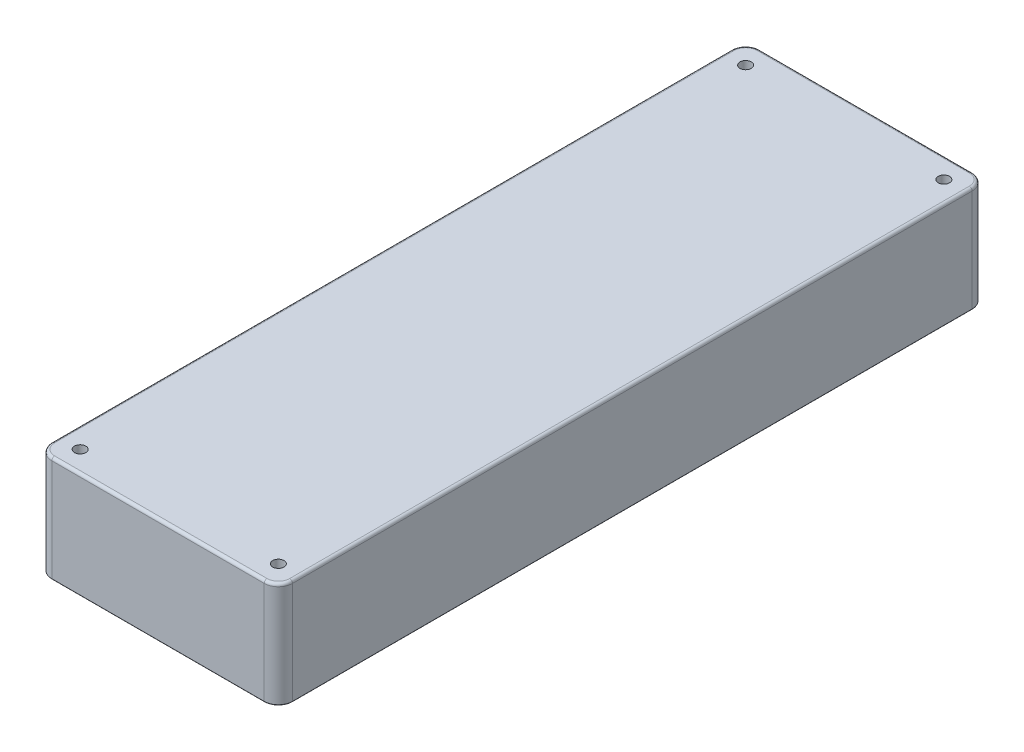
SolidWorks part; units mm, degrees
ref_plane "Front Plane" through (0, 0, 0) normal (0, 0, 1) x (1, 0, 0)
ref_plane "Top Plane" through (0, 0, 0) normal (0, 1, 0) x (1, 0, 0)
ref_plane "Right Plane" through (0, 0, 0) normal (1, 0, 0) x (0, 0, -1)
sketch "Sketch2" plane through (0, 0, 0) normal (0, 1, 0) x (1, 0, 0)
  line L1 (-42.5, 125) -> (42.5, 125)
  line L2 (-42.5, 125) -> (-42.5, -125)
  line L3 (-42.5, -125) -> (42.5, -125)
  line L4 (42.5, 125) -> (42.5, -125)
  line L5 (-42.5, 125) -> (42.5, -125) construction
  line L6 (-42.5, -125) -> (42.5, 125) construction
  point P0 (0, 0)
  dimension "D1" = 250
  dimension "D2" = 85
extrude "Boss-Extrude1" add sketch "Sketch2" along normal blind 2.25
sketch "Sketch3" plane through (0, 2.25, 0) normal (0, 1, 0) x (1, 0, 0)
  line L0 (0, 0) -> (0, 46.4308) construction
  line L1 (42.5, 125) -> (-42.5, 125) construction
  line L2 (0, 0) -> (-50.5006, 0) construction
  circle A0 centre (-35, 117.5) radius 2
  circle A1 centre (35, 117.5) radius 2
  circle A2 centre (35, -117.5) radius 2
  circle A3 centre (-35, -117.5) radius 2
  dimension "D1" = 4
  dimension "D2" = 70
  dimension "D3" = 7.5
extrude "Cut-Extrude1" cut sketch "Sketch3" against normal up to surface (2.25 mm away) up to face at (0, 0, 0)
fillet "Fillet1" radius 5 4 edges at (42.5, 1.125, 125) (-42.5, 1.125, -125) (42.5, 1.125, -125) (-42.5, 1.125, 125)
sketch "Sketch4" plane through (0, 0, 0) normal (0, -1, 0) x (1, 0, 0)
  line L0 (40.25, -120) -> (40.25, 120)
  line L1 (37.5, 122.75) -> (-37.5, 122.75)
  line L2 (-40.25, 120) -> (-40.25, -120)
  line L3 (-37.5, -122.75) -> (37.5, -122.75)
  line L4 (42.5, -120) -> (42.5, 120)
  line L5 (37.5, 125) -> (-37.5, 125)
  line L6 (-42.5, 120) -> (-42.5, -120)
  line L7 (-37.5, -125) -> (37.5, -125)
  line L8 (42.5, -120) -> (42.5, 120)
  line L9 (37.5, 125) -> (-37.5, 125)
  line L10 (-42.5, 120) -> (-42.5, -120)
  line L11 (-37.5, -125) -> (37.5, -125)
  arc A0 (40.25, 120) -> (37.5, 122.75) centre (37.5, 120) ccw
  arc A1 (-37.5, 122.75) -> (-40.25, 120) centre (-37.5, 120) ccw
  arc A2 (-40.25, -120) -> (-37.5, -122.75) centre (-37.5, -120) ccw
  arc A3 (37.5, -122.75) -> (40.25, -120) centre (37.5, -120) ccw
  arc A4 (42.5, 120) -> (37.5, 125) centre (37.5, 120) ccw
  arc A5 (-37.5, 125) -> (-42.5, 120) centre (-37.5, 120) ccw
  arc A6 (-42.5, -120) -> (-37.5, -125) centre (-37.5, -120) ccw
  arc A7 (37.5, -125) -> (42.5, -120) centre (37.5, -120) ccw
  arc A8 (42.5, 120) -> (37.5, 125) centre (37.5, 120) ccw
  arc A9 (-37.5, 125) -> (-42.5, 120) centre (-37.5, 120) ccw
  arc A10 (-42.5, -120) -> (-37.5, -125) centre (-37.5, -120) ccw
  arc A11 (37.5, -125) -> (42.5, -120) centre (37.5, -120) ccw
  dimension "D1" = 0
  dimension "D2" = 2.25
extrude "Boss-Extrude2" add sketch "Sketch4" along normal blind 35
sketch "Sketch7" plane through (0, 0, 0) normal (0, -1, 0) x (1, 0, 0)
  line L4 (37.5, 125) -> (-37.5, 125)
  line L5 (42.5, -120) -> (42.5, 120)
  line L6 (-37.5, -125) -> (37.5, -125)
  line L7 (-42.5, 120) -> (-42.5, -120)
  line L8 (37.5, 125) -> (-37.5, 125)
  line L9 (42.5, -120) -> (42.5, 120)
  line L10 (-37.5, -125) -> (37.5, -125)
  line L11 (-42.5, 120) -> (-42.5, -120)
  arc A4 (42.5, 120) -> (37.5, 125) centre (37.5, 120) ccw
  arc A5 (37.5, -125) -> (42.5, -120) centre (37.5, -120) ccw
  arc A6 (-42.5, -120) -> (-37.5, -125) centre (-37.5, -120) ccw
  arc A7 (-37.5, 125) -> (-42.5, 120) centre (-37.5, 120) ccw
  arc A8 (42.5, 120) -> (37.5, 125) centre (37.5, 120) ccw
  arc A9 (37.5, -125) -> (42.5, -120) centre (37.5, -120) ccw
  arc A10 (-42.5, -120) -> (-37.5, -125) centre (-37.5, -120) ccw
  arc A11 (-37.5, 125) -> (-42.5, 120) centre (-37.5, 120) ccw
  circle A13 centre (35, -117.5) radius 3.5
  circle A14 centre (35, -117.5) radius 3.5
  circle A320 centre (-35, -117.5) radius 3.5
  circle A321 centre (-35, -117.5) radius 3.5
  circle A323 centre (-35, 117.5) radius 3.5
  circle A324 centre (-35, 117.5) radius 3.5
  circle A326 centre (35, 117.5) radius 3.5
  circle A327 centre (35, 117.5) radius 3.5
  circle M17 centre (-35, 117.5) radius 2
  circle M18 centre (35, 117.5) radius 2
  circle M19 centre (35, -117.5) radius 2
  circle M20 centre (-35, -117.5) radius 2
  dimension "D3" = 1.5
  dimension "D1" = 0
  dimension "D2" = 1.5
  dimension "D4" = 1.5
  dimension "D5" = 1.5
extrude "Boss-Extrude5" add sketch "Sketch7" along normal blind 34 contours M20 | A14 M19 | A324 M17 | A327 M18 | A321 region at (31.599, 0, -117.5) region at (-38.401, 0, 117.5) region at (31.599, 0, 117.5) region at (-35, 0, -117.5)
fillet "Fillet2" radius 1 8 edges at (-41.0355, 2.25, -123.5355) (41.0355, 2.25, -123.5355) (41.0355, 2.25, 123.5355) (0, 2.25, 125) (-41.0355, 2.25, 123.5355) (42.5, 2.25, 0) (0, 2.25, -125) (-42.5, 2.25, 0)
fillet "Fillet3" radius 0.2 24 edges at (35, -34, -121) (35, -34, -119.5) (-35, -34, -121) (-35, -34, -119.5) (-35, -34, 114) (-35, -34, 115.5) (35, -34, 114) (35, -34, 115.5) (39.4445, -35, 121.9445) (0, -35, 122.75) (-39.4445, -35, 121.9445) (-40.25, -35, 0) (-39.4445, -35, -121.9445) (0, -35, -122.75) (39.4445, -35, -121.9445) (40.25, -35, 0) (0, -35, -125) (-41.0355, -35, -123.5355) (-42.5, -35, 0) (-41.0355, -35, 123.5355) (0, -35, 125) (41.0355, -35, 123.5355) (42.5, -35, 0) (41.0355, -35, -123.5355)
fillet "Fillet4" radius 0.2 8 edges at (-39.4445, 0, -121.9445) (-40.25, 0, 0) (-39.4445, 0, 121.9445) (0, 0, 122.75) (39.4445, 0, 121.9445) (39.4445, 0, -121.9445) (0, 0, -122.75) (40.25, 0, 0)
